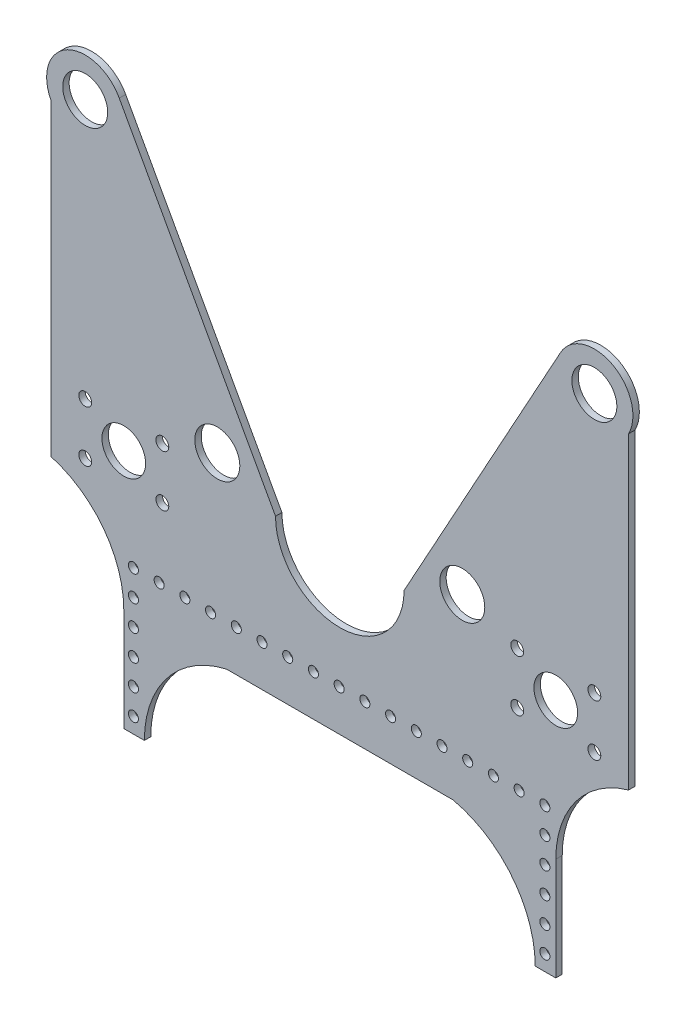
SolidWorks part; units mm, degrees
ref_plane "Front Plane" through (0, 0, 0) normal (0, 0, 1) x (1, 0, 0)
ref_plane "Top Plane" through (0, 0, 0) normal (0, 1, 0) x (1, 0, 0)
ref_plane "Right Plane" through (0, 0, 0) normal (1, 0, 0) x (0, 0, -1)
sketch "Sketch2" plane through (0, 0, 0) normal (0, 0, 1) x (1, 0, 0)
  line L0 (-106.68, -1085.9159) -> (-106.68, 48914.0841) construction
  line L1 (142.6324, 122.4629) -> (142.6324, -29.9371)
  line L2 (106.68, -1098.4025) -> (106.68, 48901.5975) construction
  line L3 (31.75, 0) -> (108.9183, 140.209)
  line L4 (0, -1082.0685) -> (0, 48917.9315) construction
  line L5 (-106.68, -44.45) -> (106.68, -44.45) construction
  line L6 (-106.68, -59.1767) -> (-106.68, -31.75)
  line L7 (0, -31.75) -> (106.68, -31.75) construction
  line L8 (106.68, -55.9582) -> (106.68, -31.75)
  line L9 (-31.75, 0) -> (-108.9183, 140.209)
  line L10 (31.75, 0) -> (108.9183, 140.209)
  line L11 (-106.68, -77.4976) -> (-106.68, -128.2976)
  line L12 (106.68, -77.4976) -> (106.68, -128.2976)
  line L13 (-106.68, -59.1767) -> (-106.68, -77.4976)
  line L14 (-55.88, -77.4976) -> (55.88, -77.4976)
  line L15 (106.68, -55.9582) -> (106.68, -77.4976)
  line L16 (-106.68, -77.4976) -> (-96.52, -77.4976) construction
  line L17 (-106.68, -77.4976) -> (-106.68, -128.2976)
  line L18 (-106.68, -128.2976) -> (-96.52, -128.2976)
  line L19 (-96.52, -77.4976) -> (-96.52, -128.2976)
  line L20 (106.68, -128.2976) -> (96.52, -128.2976)
  line L21 (55.88, -77.4976) -> (-55.88, -77.4976)
  line L22 (96.52, -77.4976) -> (96.52, -128.2976)
  line L23 (-106.68, -77.4976) -> (-96.52, -77.4976) construction
  line L24 (-96.52, -77.4976) -> (-106.68, -77.4976) construction
  line L25 (96.52, -77.4976) -> (106.68, -77.4976) construction
  line L26 (106.68, -77.4976) -> (96.52, -77.4976) construction
  line L27 (55.88, -77.4976) -> (96.52, -77.4976) construction
  line L28 (96.52, -77.4976) -> (55.88, -77.4976) construction
  line L29 (-96.52, -77.4976) -> (-55.88, -77.4976) construction
  line L30 (-55.88, -77.4976) -> (-96.52, -77.4976) construction
  line L33 (-106.68, -31.75) -> (0, -31.75) construction
  line L34 (-142.6324, 122.4629) -> (-142.6324, -29.9371)
  line L36 (-261.1394, 46.2048) -> (-243.4617, 46.2048) construction
  line L37 (-243.4617, 46.2048) -> (-243.4617, 28.5272) construction
  line L41 (-238.3305, 62.766) -> (-266.2705, 62.766) construction
  line L42 (-233.2505, 57.686) -> (-233.2505, 17.046) construction
  line L43 (-261.1394, 46.2048) -> (-261.1394, 28.5272) construction
  line L44 (-261.1394, 28.5272) -> (-243.4617, 28.5272) construction
  line L45 (-238.3305, 11.966) -> (-266.2705, 11.966) construction
  line L46 (-271.3505, 57.686) -> (-271.3505, 17.046) construction
  line L47 (-233.2505, 62.766) -> (-271.3505, 11.966) construction
  line L48 (-125.73, 3.175) -> (-125.73, -22.225) construction
  line L49 (-1101.9372, -9.525) -> (48898.0628, -9.525) construction
  line L50 (-233.2505, 11.966) -> (-271.3505, 62.766) construction
  line L51 (-239.6005, 56.416) -> (-239.6005, 18.316) construction
  line L52 (-265.0005, 56.416) -> (-239.6005, 56.416) construction
  line L53 (-125.73, 3.175) -> (-106.68, 3.175) construction
  arc A0 (-31.75, 0) -> (31.75, 0) centre (0, 0) ccw
  arc A1 (-108.9183, 140.209) -> (-142.6324, 122.4629) centre (-125.7268, 131.2438) ccw
  circle A2 centre (-60.4845, 12.7) radius 11.1125
  arc A3 (31.75, 0) -> (0, 31.75) centre (0, 0) ccw construction
  arc A4 (0, 31.75) -> (-31.75, 0) centre (0, 0) ccw construction
  arc A5 (-96.52, -128.2976) -> (-55.88, -77.4976) centre (-44.45, -128.2976) cw
  arc A6 (96.52, -128.2976) -> (55.88, -77.4976) centre (44.45, -128.2976) ccw
  circle A7 centre (-125.7268, 131.2438) radius 11.1125
  circle A9 centre (-60.4845, 12.7) radius 19.05 construction
  circle A10 centre (60.4845, 12.7) radius 19.05 construction
  arc A11 (108.9183, 140.209) -> (142.6324, 122.4629) centre (125.7268, 131.2438) cw
  circle A12 centre (125.7268, 131.2438) radius 11.1125
  circle A34 centre (-101.9175, -57.15) radius 2.4892
  arc A40 (-142.6324, 122.4629) -> (-108.9183, 140.209) centre (-125.7268, 131.2438) ccw construction
  arc A41 (142.6324, 122.4629) -> (108.9183, 140.209) centre (125.7268, 131.2438) cw construction
  circle A42 centre (60.4845, 12.7) radius 11.1125
  circle A43 centre (-89.2175, -57.15) radius 2.4892
  circle A44 centre (-76.5175, -57.15) radius 2.4892
  circle A45 centre (-63.8175, -57.15) radius 2.4892
  circle A46 centre (-51.1175, -57.15) radius 2.4892
  circle A47 centre (-38.4175, -57.15) radius 2.4892
  circle A48 centre (-25.7175, -57.15) radius 2.4892
  circle A49 centre (-13.0175, -57.15) radius 2.4892
  circle A50 centre (-0.3175, -57.15) radius 2.4892
  circle A51 centre (12.3825, -57.15) radius 2.4892
  circle A52 centre (25.0825, -57.15) radius 2.4892
  circle A53 centre (37.7825, -57.15) radius 2.4892
  circle A54 centre (50.4825, -57.15) radius 2.4892
  circle A55 centre (63.1825, -57.15) radius 2.4892
  circle A56 centre (75.8825, -57.15) radius 2.4892
  circle A57 centre (88.5825, -57.15) radius 2.4892
  circle A58 centre (101.2825, -57.15) radius 2.4892
  circle A59 centre (-101.9175, -69.85) radius 2.4892
  circle A60 centre (-101.9175, -82.55) radius 2.4892
  circle A61 centre (-101.9175, -95.25) radius 2.4892
  circle A62 centre (-101.9175, -107.95) radius 2.4892
  circle A63 centre (-101.9175, -120.65) radius 2.4892
  circle A64 centre (101.2825, -69.85) radius 2.4892
  circle A65 centre (101.2825, -82.55) radius 2.4892
  circle A66 centre (101.2825, -95.25) radius 2.4892
  circle A67 centre (101.2825, -107.95) radius 2.4892
  circle A68 centre (101.2825, -120.65) radius 2.4892
  arc A69 (-106.68, -77.4976) -> (-142.6324, -29.9371) centre (-156.1145, -77.4976) ccw
  arc A70 (106.68, -77.4976) -> (142.6324, -29.9371) centre (156.1145, -77.4976) cw
  circle A73 centre (-106.68, -9.525) radius 10.795
  circle A91 centre (-125.73, 3.175) radius 3.175
  circle A92 centre (-125.73, -22.225) radius 3.175
  circle A93 centre (-87.63, -22.225) radius 3.175
  circle A94 centre (-87.63, 3.175) radius 3.175
  circle A95 centre (87.63, -22.225) radius 3.175
  circle A96 centre (87.63, 3.175) radius 3.175
  circle A97 centre (106.68, -9.525) radius 10.795
  circle A98 centre (125.73, -22.225) radius 3.175
  circle A99 centre (125.73, 3.175) radius 3.175
  arc A100 (-260.1552, 27.7564) -> (-262.1235, 29.2979) centre (-261.1394, 28.5272) ccw construction
  arc A101 (-262.1235, 29.2979) -> (-260.1552, 27.7564) centre (-261.1394, 28.5272) ccw construction
  arc A102 (-244.4458, 29.2979) -> (-242.4776, 27.7564) centre (-243.4617, 28.5272) ccw construction
  arc A103 (-242.4776, 27.7564) -> (-244.4458, 29.2979) centre (-243.4617, 28.5272) ccw construction
  arc A104 (-242.4776, 45.4341) -> (-244.4458, 46.9756) centre (-243.4617, 46.2048) ccw construction
  arc A105 (-244.4458, 46.9756) -> (-242.4776, 45.4341) centre (-243.4617, 46.2048) ccw construction
  arc A106 (-262.1235, 46.9756) -> (-260.1552, 45.4341) centre (-261.1394, 46.2048) ccw construction
  arc A107 (-260.1552, 45.4341) -> (-262.1235, 46.9756) centre (-261.1394, 46.2048) ccw construction
  circle A108 centre (-252.3005, 37.366) radius 7.3172 construction
  circle A109 centre (-265.0005, 56.416) radius 3.175 construction
  circle A110 centre (-239.6005, 56.416) radius 3.175 construction
  circle A111 centre (-239.6005, 18.316) radius 3.175 construction
  circle A112 centre (-265.0005, 18.316) radius 3.175 construction
  arc A113 (-266.2705, 11.966) -> (-271.3505, 17.046) centre (-266.2705, 17.046) cw construction
  arc A114 (-233.2505, 17.046) -> (-238.3305, 11.966) centre (-238.3305, 17.046) cw construction
  arc A115 (-238.3305, 62.766) -> (-233.2505, 57.686) centre (-238.3305, 57.686) cw construction
  arc A116 (-266.2705, 62.766) -> (-271.3505, 57.686) centre (-266.2705, 57.686) ccw construction
  point P154 (-125.73, -9.525)
  point P169 (0, 0)
  dimension "D7" = 12.7
  dimension "D8" = 4.7625
  dimension "D9" = 25.4
  dimension "D3" = 44.45
  dimension "D14" = 106.68
  dimension "D17" = 38.1
  dimension "D5" = 52.07
  dimension "D15" = 31.75
  dimension "D16" = 22.225
  dimension "D18" = 22.225
  dimension "D19" = 19.05
  dimension "D23" = 4.9784
  dimension "D24" = 49.4345
  dimension "D21" = 125.7268
  dimension "D27" = 22.225
  dimension "D28" = 21.59
  dimension "D33" = 6.35
  dimension "D35" = 8.8388
  dimension "D37" = 8.8388
  dimension "D46" = 6.35
  dimension "D34" = 6.35
  dimension "D36" = 1.25
  dimension "D38" = 5.08
  dimension "D1" = 28.828
  dimension "D4" = 45.7476
  dimension "D6" = 88.9
  dimension "D10" = 17
  dimension "D11" = 12.7
  dimension "D12" = 12.7
  dimension "D13" = 111.76
  dimension "D20" = 142.6324
  dimension "D22" = 6
  dimension "D25" = 152.4
  dimension "D26" = 12.7
  dimension "D32" = 6.35
  dimension "D29" = 17.6777
  dimension "D30" = 50.8
  dimension "D31" = 38.1
  dimension "D39" = 25.4
  dimension "D40" = 38.1
  dimension "D41" = 16.9024
extrude "Boss-Extrude1" add sketch "Sketch2" along normal blind 3.175 contours A11 L3 A0 L9 A1 L6 L13 L11 L18 A5 L14 A6 L20 L12 L15 L8 A68 A67 A66 A65 A64 A63 A62 A61 A60 A59 A58 A57 A56 A55 region at (138.6142, 46.2629, 0)
